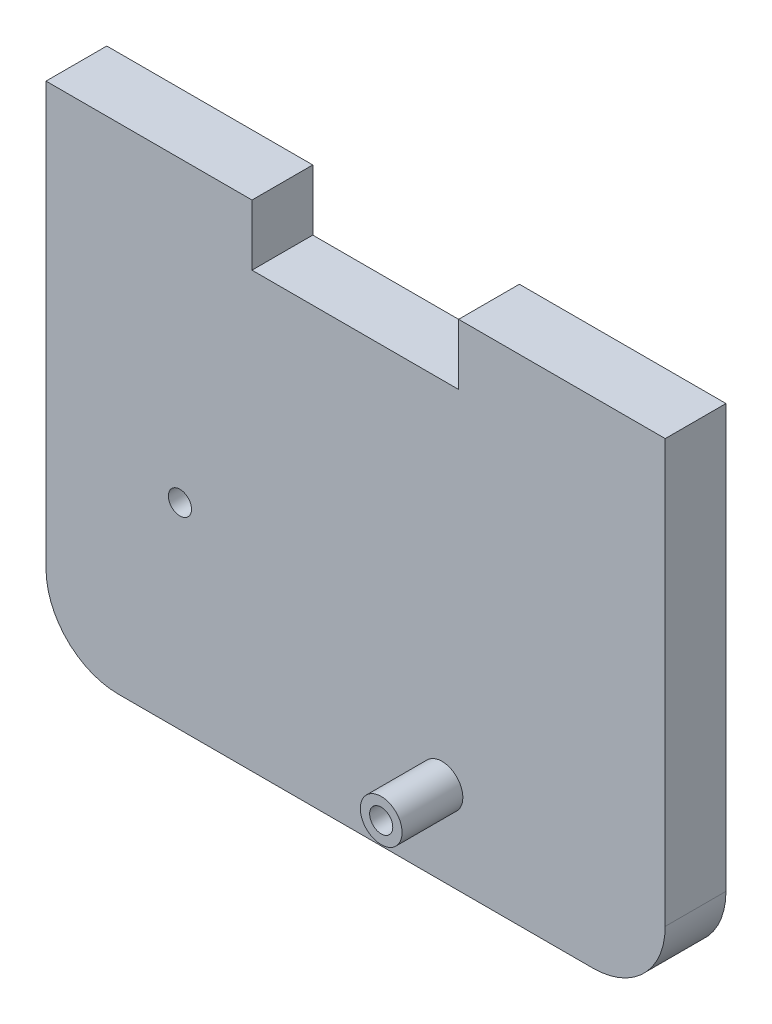
SolidWorks part; units mm, degrees
material "Teak"
ref_plane "Front Plane" through (0, 0, 0) normal (0, 0, 1) x (1, 0, 0)
ref_plane "Top Plane" through (0, 0, 0) normal (0, 1, 0) x (1, 0, 0)
ref_plane "Right Plane" through (0, 0, 0) normal (1, 0, 0) x (0, 0, -1)
sketch "Sketch1" plane through (0, 0, 0) normal (0, 0, 1) x (1, 0, 0)
  line L1 (-30.5325, 25.3111) -> (23.8235, 25.3111)
  line L2 (-30.5325, 25.3111) -> (-30.5325, -18.1229)
  line L3 (-30.5325, -18.1229) -> (23.8235, -18.1229)
  line L4 (23.8235, 25.3111) -> (23.8235, -18.1229)
  dimension "D1" = 43.434
  dimension "D2" = 54.356
extrude "Boss-Extrude1" add sketch "Sketch1" along normal blind 5.334 contours L1 L4 L3 L2
sketch "Sketch2" plane through (0, 0, 5.334) normal (0, 0, 1) x (1, 0, 0)
  line L0 (-30.5325, 25.3111) -> (23.8235, 25.3111) construction
  line L1 (-12.4506, 25.3111) -> (5.6865, 25.3111)
  line L2 (-12.4506, 25.3111) -> (-12.4506, 19.9771)
  line L3 (-12.4506, 19.9771) -> (5.6865, 19.9771)
  line L4 (5.6865, 25.3111) -> (5.6865, 19.9771)
  line L5 (-12.4506, 19.9771) -> (-30.5325, 19.9771) construction
  line L6 (-30.5325, 25.3111) -> (-30.5325, -18.1229) construction
  line L7 (5.6865, 19.9771) -> (23.8235, 19.9771) construction
  line L8 (23.8235, 25.3111) -> (23.8235, -18.1229) construction
  dimension "D1" = 5.334
extrude "Cut-Extrude1" cut sketch "Sketch2" against normal through all
fillet "Fillet1" radius 6.35 2 edges at (-30.5325, -18.1229, 2.667) (23.8235, -18.1229, 2.667)
sketch "Sketch3" plane through (0, 0, 5.334) normal (0, 0, 1) x (1, 0, 0)
  line L8 (-30.5325, 25.3111) -> (-30.5325, -11.7729)
  line L9 (-24.1825, -18.1229) -> (17.4735, -18.1229)
  line L10 (23.8235, -11.7729) -> (23.8235, 25.3111)
  line L11 (23.8235, 25.3111) -> (5.6865, 25.3111)
  line L12 (5.6865, 25.3111) -> (5.6865, 19.9771)
  line L13 (5.6865, 19.9771) -> (-12.4506, 19.9771)
  line L14 (-12.4506, 19.9771) -> (-12.4506, 25.3111)
  line L15 (-12.4506, 25.3111) -> (-30.5325, 25.3111)
  line L16 (-30.5325, 25.3111) -> (-30.5325, -11.7729)
  line L17 (-24.1825, -18.1229) -> (17.4735, -18.1229)
  line L18 (23.8235, -11.7729) -> (23.8235, 25.3111)
  line L19 (23.8235, 25.3111) -> (5.6865, 25.3111)
  line L20 (5.6865, 25.3111) -> (5.6865, 19.9771)
  line L21 (5.6865, 19.9771) -> (-12.4506, 19.9771)
  line L22 (-12.4506, 19.9771) -> (-12.4506, 25.3111)
  line L23 (-12.4506, 25.3111) -> (-30.5325, 25.3111)
  circle A0 centre (-18.7754, -0.8561) radius 1.5 construction
  circle A1 centre (4.2246, -10.8561) radius 1.5 construction
  arc A2 (-30.5325, -11.7729) -> (-24.1825, -18.1229) centre (-24.1825, -11.7729) ccw
  arc A3 (17.4735, -18.1229) -> (23.8235, -11.7729) centre (17.4735, -11.7729) ccw
  arc A4 (-30.5325, -11.7729) -> (-24.1825, -18.1229) centre (-24.1825, -11.7729) ccw
  arc A5 (17.4735, -18.1229) -> (23.8235, -11.7729) centre (17.4735, -11.7729) ccw
  circle A6 centre (-18.7754, -0.8561) radius 1.5
  circle A7 centre (4.2246, -10.8561) radius 1.5
  dimension "D1" = 0
extrude "Cut-Extrude3" cut sketch "Sketch3" against normal through all contours A6 | A7
sketch "Sketch4" plane through (0, 0, 5.334) normal (0, 0, 1) x (1, 0, 0)
  circle A0 centre (-18.7754, -0.8561) radius 1.016
  circle A1 centre (-18.7754, -0.8561) radius 2.1298
  dimension "D1" = 2.032
extrude "Boss-Extrude2" add sketch "Sketch4" against normal blind 5.334
sketch "Sketch5" plane through (0, 0, 5.334) normal (0, 0, 1) x (1, 0, 0)
  circle A0 centre (4.2246, -10.8561) radius 1.016
  circle A1 centre (4.2246, -10.8561) radius 1.8335
extrude "Boss-Extrude3" add sketch "Sketch5" along normal blind 5.334
equation "\"MDF\"= .21in"
equation "\"Foamcore\"= .13in"
equation "\"Gmaterial\"= \"MDF\""
equation "\"D1@Sketch1\"=\"MDF\"+1.5"
equation "\"D1@Boss-Extrude1\"=\"MDF\""
equation "\"D1@Sketch2\"=\"MDF\""
equation "\"D1@Boss-Extrude2\"=\"MDF\""
